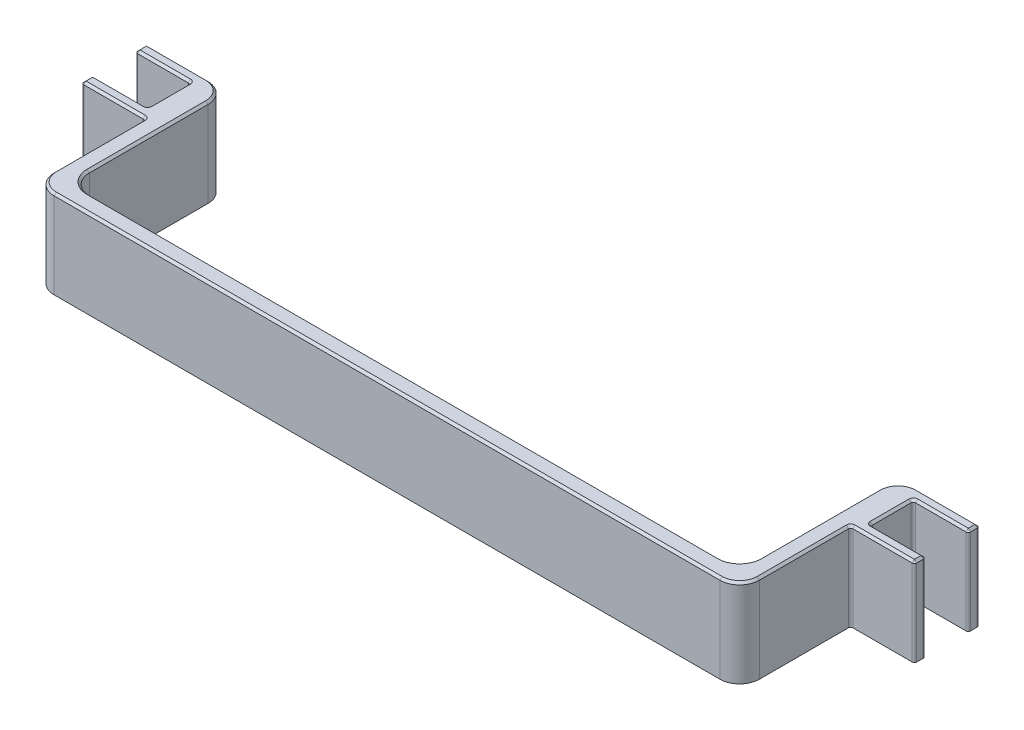
SolidWorks part; units mm, degrees
ref_plane "Front" through (0, 0, 0) normal (0, 0, 1) x (1, 0, 0)
ref_plane "Top" through (0, 0, 0) normal (0, 1, 0) x (1, 0, 0)
ref_plane "Right" through (0, 0, 0) normal (1, 0, 0) x (0, 0, -1)
sketch "Sketch1" plane through (0, 0, 0) normal (0, 1, 0) x (1, 0, 0)
  line L0 (152.4, 0) -> (-152.4, 0)
  line L1 (-152.4, 0) -> (-152.4, 72)
  line L2 (-152.4, 72) -> (-189.4, 72)
  line L3 (-189.4, 72) -> (-189.4, 67)
  line L4 (-189.4, 67) -> (-164.4, 67)
  line L5 (-164.4, 67) -> (-164.4, 47.5)
  line L6 (-164.4, 47.5) -> (-189.4, 47.5)
  line L7 (-189.4, 47.5) -> (-189.4, 42.5)
  line L8 (-189.4, 42.5) -> (-160.4, 42.5)
  line L9 (-160.4, 42.5) -> (-160.4, -8)
  line L10 (-160.4, -8) -> (160.4, -8)
  line L11 (0, 126.7654) -> (0, -150.0124) construction
  line L12 (160.4, 42.5) -> (160.4, -8)
  line L13 (189.4, 42.5) -> (160.4, 42.5)
  line L14 (189.4, 47.5) -> (189.4, 42.5)
  line L15 (164.4, 47.5) -> (189.4, 47.5)
  line L16 (164.4, 67) -> (164.4, 47.5)
  line L17 (189.4, 67) -> (164.4, 67)
  line L18 (189.4, 72) -> (189.4, 67)
  line L19 (152.4, 72) -> (189.4, 72)
  line L20 (152.4, 0) -> (152.4, 72)
  point P16 (0, -8)
  point P25 (0, 0)
  dimension "D1" = 304.8
  dimension "D2" = 8
  dimension "D3" = 8
  dimension "D4" = 12
  dimension "D5" = 19.5
  dimension "D6" = 5
  dimension "D7" = 25
  dimension "D8" = 80
extrude "Boss-Extrude1" add sketch "Sketch1" along normal blind 40
fillet "Fillet1" radius 9 6 edges at (-152.4, 20, -72) (152.4, 20, -72) (152.4, 20, 0) (160.4, 20, 8) (-152.4, 20, 0) (-160.4, 20, 8)
fillet "Fillet2" radius 1 14 edges at (189.4, 20, -72) (189.4, 20, -67) (164.4, 20, -67) (164.4, 20, -47.5) (189.4, 20, -47.5) (189.4, 20, -42.5) (160.4, 20, -42.5) (-160.4, 20, -42.5) (-189.4, 20, -47.5) (-164.4, 20, -47.5) (-164.4, 20, -67) (-189.4, 20, -67) (-189.4, 20, -72) (-189.4, 20, -42.5)
chamfer "Chamfer1" distance 1 angle 45 40 edges at (174.9, 40, -42.5) (189.1071, 40, -42.7929) (160.6929, 40, -42.2071) (189.4, 40, -45) (160.4, 40, -21.25) (189.1071, 40, -47.2071) (157.764, 40, 5.364) (176.9, 40, -47.5) (0, 40, 8) (164.6929, 40, -47.7929) (-157.764, 40, 5.364) (164.4, 40, -57.25) (-160.4, 40, -21.25) (164.6929, 40, -66.7071) (-160.6929, 40, -42.2071) (176.9, 40, -67) (-174.9, 40, -42.5) (189.1071, 40, -67.2929) (-189.1071, 40, -42.7929) (189.4, 40, -69.5) (-189.4, 40, -45) (189.1071, 40, -71.7071) (-189.1071, 40, -47.2071) (174.9, 40, -72) (-176.9, 40, -47.5) (155.036, 40, -69.364) (-164.6929, 40, -47.7929) (152.4, 40, -36) (-164.4, 40, -57.25) (149.764, 40, -2.636) (-164.6929, 40, -66.7071) (0, 40, 0) (-176.9, 40, -67) (-149.764, 40, -2.636) (-189.1071, 40, -67.2929) (-152.4, 40, -36) (-189.4, 40, -69.5) (-155.036, 40, -69.364) (-189.1071, 40, -71.7071) (-174.9, 40, -72)
